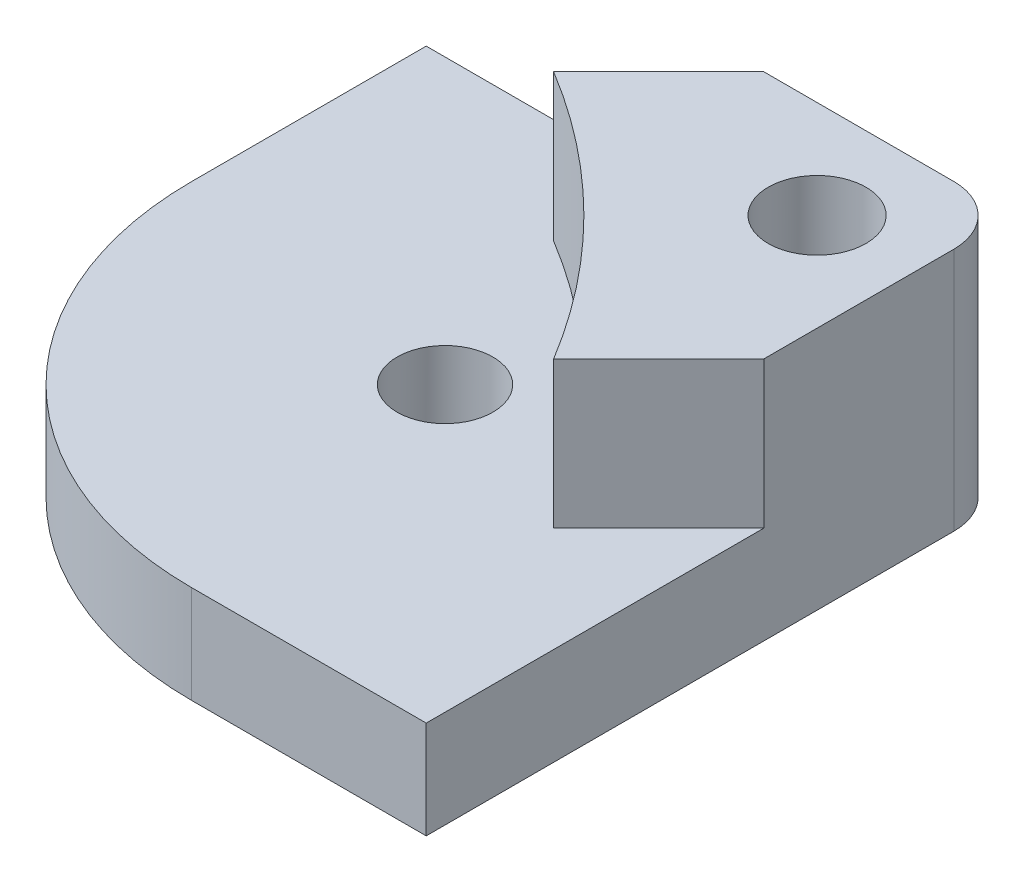
SolidWorks part; units mm, degrees
note: '?' marks a value the reader was unsure of. The reader was unsure of these and kept them because the rebuilt part matched: shared geometry of "Sketch11<4>".
ref_plane "Front Plane" through (0, 0, 0) normal (0, 0, 1) x (1, 0, 0)
ref_plane "Top Plane" through (0, 0, 0) normal (0, 1, 0) x (1, 0, 0)
ref_plane "Right Plane" through (0, 0, 0) normal (1, 0, 0) x (0, 0, -1)
sketch "Sketch1" plane through (0, 0, 0) normal (0, 1, 0) x (1, 0, 0)
  line L1 (-95.25, -95.25) -> (95.25, -95.25)
  line L2 (-95.25, -95.25) -> (-95.25, 95.25)
  line L3 (-95.25, 95.25) -> (95.25, 95.25)
  line L4 (95.25, -95.25) -> (95.25, 95.25)
  line L5 (-95.25, -95.25) -> (95.25, 95.25) construction
  line L6 (-95.25, 95.25) -> (95.25, -95.25) construction
  point P0 (0, 0)
  dimension "D1" = 190.5
  dimension "D2" = 190.5
extrude "Boss-Extrude1" add sketch "Sketch1" along normal blind 12.7
fillet "Fillet1" radius 7.62 4 edges at (-95.25, 6.35, 95.25) (95.25, 6.35, 95.25) (95.25, 6.35, -95.25) (-95.25, 6.35, -95.25)
ref_plane "Plane1" through (12.7, 0, 0) normal (1, 0, 0) x (0, 0, -1)
sketch "Sketch6" plane through (0, 12.7, 0) normal (0, 1, 0) x (1, 0, 0)
  line L0 (-95.25, 87.63) -> (-95.25, -87.63) construction
  line L1 (-82.55, -82.55) -> (82.55, -82.55)
  line L2 (-82.55, -82.55) -> (-82.55, 82.55)
  line L3 (-82.55, 82.55) -> (82.55, 82.55)
  line L4 (82.55, -82.55) -> (82.55, 82.55)
  line L5 (-82.55, -82.55) -> (82.55, 82.55) construction
  line L6 (-82.55, 82.55) -> (82.55, -82.55) construction
  line L7 (-87.63, -95.25) -> (87.63, -95.25) construction
  point P0 (0, 0)
  dimension "D1" = 12.7
  dimension "D2" = 12.7
sketch "Sketch7" plane through (0, 12.7, 0) normal (0, 1, 0) x (1, 0, 0)
  line L0 (95.25, 95.25) -> (-95.25, -95.25) construction
  line L1 (62.9211, 95.25) -> (49.2652, 81.5941)
  line L2 (81.5941, 49.2652) -> (95.25, 62.9211)
  line L8 (95.25, -87.63) -> (95.25, 87.63)
  line L9 (87.63, 95.25) -> (-87.63, 95.25)
  line L14 (-95.25, 87.63) -> (-95.25, -87.63)
  line L15 (-87.63, -95.25) -> (87.63, -95.25)
  line L16 (95.25, -87.63) -> (95.25, 87.63)
  line L17 (87.63, 95.25) -> (-87.63, 95.25)
  line L22 (-95.25, 87.63) -> (-95.25, -87.63)
  line L23 (-87.63, -95.25) -> (87.63, -95.25)
  circle A0 centre (0, 0) radius 95.3135
  arc A5 (95.25, 87.63) -> (87.63, 95.25) centre (87.63, 87.63) ccw
  arc A6 (-87.63, 95.25) -> (-95.25, 87.63) centre (-87.63, 87.63) ccw
  arc A7 (-95.25, -87.63) -> (-87.63, -95.25) centre (-87.63, -87.63) ccw
  arc A8 (87.63, -95.25) -> (95.25, -87.63) centre (87.63, -87.63) ccw
  arc A9 (95.25, 87.63) -> (87.63, 95.25) centre (87.63, 87.63) ccw
  arc A10 (-87.63, 95.25) -> (-95.25, 87.63) centre (-87.63, 87.63) ccw
  arc A11 (-95.25, -87.63) -> (-87.63, -95.25) centre (-87.63, -87.63) ccw
  arc A12 (87.63, -95.25) -> (95.25, -87.63) centre (87.63, -87.63) ccw
  line M17 (95.25, -87.63) -> (95.25, 87.63)
  arc M18 (95.25, 87.63) -> (87.63, 95.25) centre (87.63, 87.63) ccw
  line M19 (87.63, 95.25) -> (-87.63, 95.25)
  dimension "D3" = 190.627
  dimension "D2" = 190.5
  dimension "D4" = 45
  dimension "D5" = 7.62
  dimension "D6" = 7.62
  dimension "D7" = 22.86
  dimension "D8" = 22.86
  dimension "D1" = 0
extrude "Boss-Extrude3" add sketch "Sketch7" along normal blind 19.05 contours L0 A9 L1 A0 M19 | L0 A0 L2 M18 M17
ref_axis "Axis1" through (0, 195.7992, 0) along (0, -1, 0)?
pattern_circular "CirPattern1" count 4 over 360 about axis through (0, 0, 0) along (0, 1, 0) of "Boss-Extrude3"
sketch "Sketch8" plane through (0, 12.7, 0) normal (0, 1, 0) x (1, 0, 0)
  circle A0 centre (0, 0) radius 82.55
  circle A1 centre (0, 82.55) radius 6.223
  circle A2 centre (58.3717, 58.3717) radius 6.223
  circle A3 centre (82.55, 0) radius 6.223
  circle A4 centre (58.3717, -58.3717) radius 6.223
  circle A5 centre (0, -82.55) radius 6.223
  circle A6 centre (-58.3717, -58.3717) radius 6.223
  circle A7 centre (-82.55, 0) radius 6.223
  circle A8 centre (-58.3717, 58.3717) radius 6.223
  point P21 (0, 0)
  dimension "D1" = 165.1
  dimension "D2" = 12.446
  dimension "D3" = 8
extrude "Cut-Extrude2" cut sketch "Sketch8" against normal blind 25.4 contours A1 | A8 | A7 | A6 | A5 | A4 | A3 | A2
sketch "Sketch10" plane through (0, 12.7, 0) normal (0, 1, 0) x (1, 0, 0)
  line L12 (95.25, -62.9211) -> (95.25, 62.9211) construction
  line L21 (95.25, 38.1) -> (38.1, 38.1)
  line L22 (95.25, 38.1) -> (95.25, 95.25)
  line L23 (95.25, 95.25) -> (38.1, 95.25)
  line L24 (38.1, 38.1) -> (38.1, 95.25)
  line L25 (62.9211, 95.25) -> (-62.9211, 95.25) construction
  line L26 (-62.9211, -95.25) -> (62.9211, -95.25) construction
  line L27 (95.25, 95.25) -> (-95.25, 95.25)
  line L28 (95.25, 95.25) -> (95.25, -95.25)
  line L29 (95.25, -95.25) -> (-95.25, -95.25)
  line L30 (-95.25, 95.25) -> (-95.25, -95.25)
  line L31 (-95.25, 62.9211) -> (-95.25, -62.9211) construction
  circle M5 centre (0, 82.55) radius 6.223
  circle M6 centre (-58.3717, 58.3717) radius 6.223
  circle M7 centre (-82.55, 0) radius 6.223
  circle M8 centre (-58.3717, -58.3717) radius 6.223
  circle M9 centre (0, -82.55) radius 6.223
  circle M10 centre (58.3717, -58.3717) radius 6.223
  circle M11 centre (82.55, 0) radius 6.223
  line M13 (-62.9211, 95.25) -> (-49.2652, 81.5941)
  arc M14 (-49.2652, 81.5941) -> (-81.5941, 49.2652) centre (0, 0) ccw
  line M15 (-81.5941, 49.2652) -> (-95.25, 62.9211)
  line M16 (-95.25, 62.9211) -> (-95.25, -62.9211)
  line M17 (-95.25, -62.9211) -> (-81.5941, -49.2652)
  arc M18 (-81.5941, -49.2652) -> (-49.2652, -81.5941) centre (0, 0) ccw
  line M19 (-49.2652, -81.5941) -> (-62.9211, -95.25)
  line M20 (-62.9211, -95.25) -> (62.9211, -95.25)
  line M21 (62.9211, -95.25) -> (49.2652, -81.5941)
  arc M22 (49.2652, -81.5941) -> (81.5941, -49.2652) centre (0, 0) ccw
  line M23 (81.5941, -49.2652) -> (95.25, -62.9211)
  line M24 (95.25, -62.9211) -> (95.25, 62.9211)
  line M28 (62.9211, 95.25) -> (-62.9211, 95.25)
  dimension "D2" = 57.15
  dimension "D1" = 57.15
sketch "Sketch11" plane through (0, 31.75, 0) normal (0, 1, 0) x (1, 0, 0)
  line L0 (87.63, 95.25) -> (62.9211, 95.25) construction
  line L1 (95.25, 62.9211) -> (95.25, 87.63) construction
  circle A0 centre (82.55, 82.55) radius 6.35
  circle A1 centre (82.55, 82.55) radius 3.2385
  dimension "D1" = 12.7
  dimension "D4" = 6.477
  dimension "D2" = 12.7
  dimension "D3" = 12.7
extrude "Cut-Extrude6" cut sketch "Sketch10" against normal through all both and the other way through all contours L21 L24 M28 M13 M14 M15 M16 M17 M18 M19 M20 M21 M22 M23 M24 M5 M7 M9 M11 M10 M8 M6
extrude "Cut-Extrude7" cut sketch "Sketch11" against normal up to surface (19.05 mm away) up to face at (58.3717, 12.7, -52.1487)
extrude "Cut-Extrude8" cut sketch "Sketch11<4>" against normal through all contours A1
sketch "Sketch11<4>" plane through (0, 31.75, 0) normal (0, 1, 0) x (1, 0, 0) same geometry as "Sketch11"
fillet "Fillet3" radius 12.7 3 edges at (95.25, 6.35, -38.1) (38.1, 6.35, -38.1) (38.1, 6.35, -95.25)
sketch "Sketch12" plane through (0, 12.7, 0) normal (0, 1, 0) x (1, 0, 0)
  line L1 (87.63, 95.25) -> (19.05, 95.25)
  line L2 (95.25, 87.63) -> (95.25, 64.77)
  line L3 (95.25, 64.77) -> (19.05, 64.77)
  line L4 (19.05, 95.25) -> (19.05, 64.77)
  line L5 (95.25, 62.9211) -> (95.25, 87.63) construction
  line L7 (87.63, 95.25) -> (64.77, 95.25)
  line L8 (95.25, 87.63) -> (95.25, 19.05)
  line L9 (95.25, 19.05) -> (64.77, 19.05)
  line L10 (64.77, 95.25) -> (64.77, 19.05)
  arc A0 (95.25, 87.63) -> (87.63, 95.25) centre (87.63, 87.63) ccw construction
  arc A1 (95.25, 87.63) -> (87.63, 95.25) centre (87.63, 87.63) ccw
  arc A2 (19.05, 64.77) -> (64.77, 19.05) centre (64.77, 64.77) ccw
  line M9 (50.8, 38.1) -> (82.55, 38.1)
  arc M10 (82.55, 38.1) -> (95.25, 50.8) centre (82.55, 50.8) ccw
  arc M16 (50.8, 95.25) -> (38.1, 82.55) centre (50.8, 82.55) ccw
  line M17 (38.1, 82.55) -> (38.1, 50.8)
  arc M18 (38.1, 50.8) -> (50.8, 38.1) centre (50.8, 50.8) ccw
  dimension "D1" = 76.2
  dimension "D2" = 76.2
  dimension "D3" = 30.48
  dimension "D4" = 30.48
extrude "Boss-Extrude5" add sketch "Sketch12" against normal up to surface (12.7 mm away) contours L1 L4 L3 M17 M16 | L10 L9 L8 M9 M10 | L3 A2 L10 M9 M18 M17 up to face at (82.55, 0, -79.3115)
